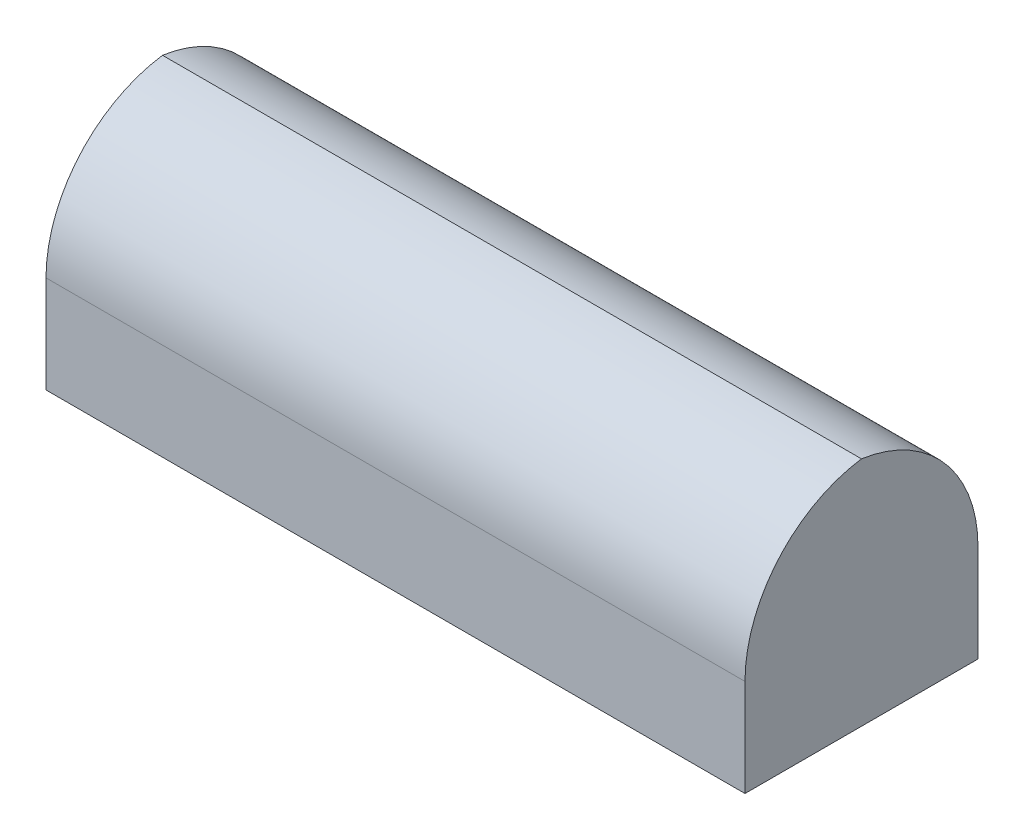
SolidWorks part; units mm, degrees
ref_plane "Спереди" through (0, 0, 0) normal (0, 0, 1) x (1, 0, 0)
ref_plane "Сверху" through (0, 0, 0) normal (0, 1, 0) x (1, 0, 0)
ref_plane "Справа" through (0, 0, 0) normal (1, 0, 0) x (0, 0, -1)
sketch "Эскиз1" plane through (0, 4.85, 0) normal (0, 1, 0) x (1, 0, 0)
  line L4 (4.65, 1.35) -> (4.65, 2.55)
  line L5 (4.65, 2.55) -> (1.05, 2.55)
  line L6 (1.05, 2.55) -> (1.05, 1.35)
  line L7 (1.05, 1.35) -> (4.65, 1.35)
  line L8 (4.65, 1.35) -> (4.65, 2.55)
  line L9 (4.65, 2.55) -> (1.05, 2.55)
  line L10 (1.05, 2.55) -> (1.05, 1.35)
  line L11 (1.05, 1.35) -> (4.65, 1.35)
  dimension "D1" = 0
extrude "Бобышка-Вытянуть1" add sketch "Эскиз1" along normal blind 1.2
fillet "Скругление1" radius 0.7 2 edges at (2.85, 6.05, -1.35) (2.85, 6.05, -2.55)
